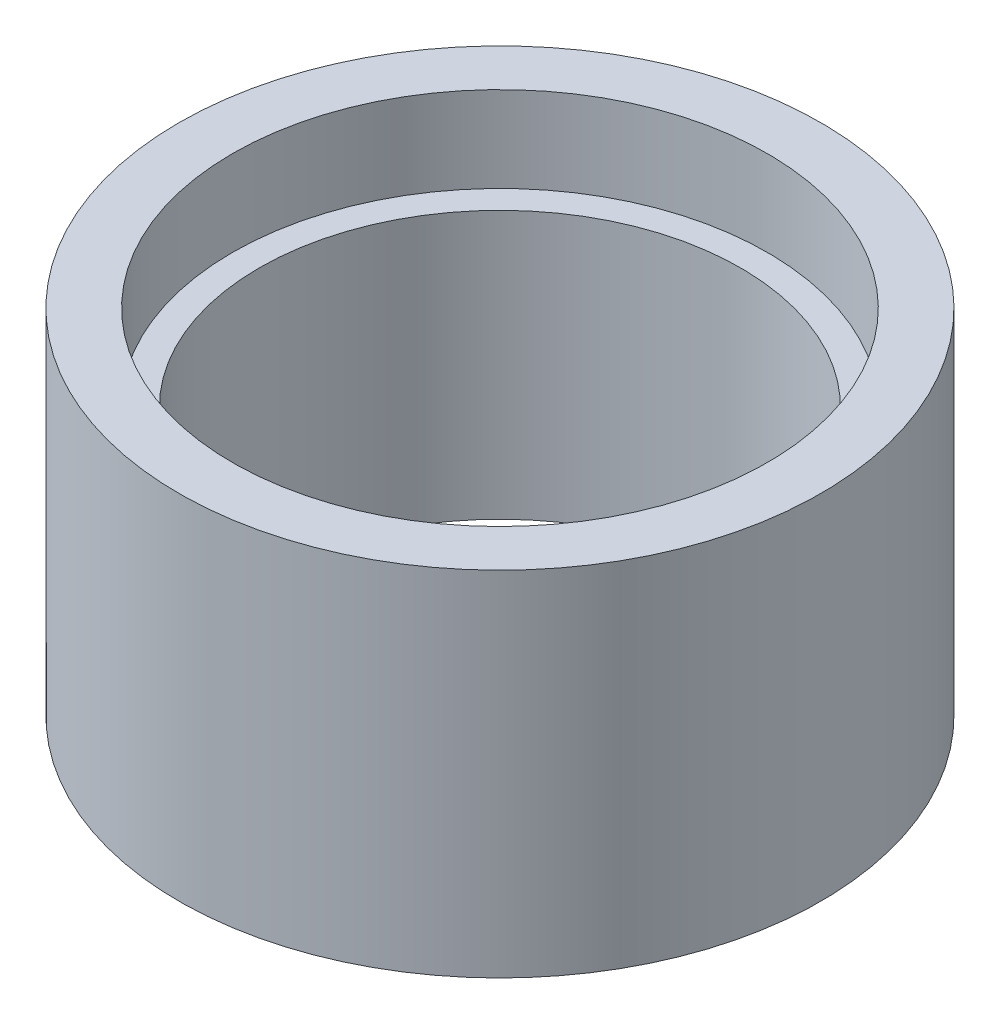
SolidWorks part; units mm, degrees
material "POM Acetal Copolymer"
ref_plane "Front" through (0, 0, 0) normal (0, 0, 1) x (1, 0, 0)
ref_plane "Top" through (0, 0, 0) normal (0, 1, 0) x (1, 0, 0)
ref_plane "Right" through (0, 0, 0) normal (1, 0, 0) x (0, 0, -1)
ref_axis "Center Axis" through (0, 0, 55) along (0, 0, -1)
sketch "Sketch1" plane through (0, 0, 0) normal (0, 0, 1) x (1, 0, 0)
  line L1 (0, 0) -> (12, 0)
  line L2 (0, 0) -> (0, -13.2)
  line L3 (0, -13.2) -> (12, -13.2)
  line L4 (12, 0) -> (12, -13.2)
  line L5 (0, 0) -> (10, 0)
  line L6 (0, 0) -> (0, -3.2)
  line L7 (0, -3.2) -> (10, -3.2)
  line L8 (10, 0) -> (10, -3.2)
  line L9 (12, -13.2) -> (9, -13.2)
  line L10 (12, -13.2) -> (12, -3.2)
  line L11 (12, -3.2) -> (9, -3.2)
  line L12 (9, -13.2) -> (9, -3.2)
  dimension "D1" = 12
  dimension "D2" = 2
  dimension "D3" = 3.2
  dimension "D4" = 1
  dimension "D5" = 10
revolve "Revolve1" add sketch "Sketch1" angle 360 about L2 region at (11, -1.6, 0) region at (10.5, -8.2, 0)
equation "\"WallThickness\" = 2mm"
equation "\"D1@Sketch1\"=\"PiezoDiameter\"/2 +\"WallThickness\""
equation "\"PiezoDiameter\"= 20mm"
equation "\"PiezoThickness\"= 2.7mm"
equation "\"BackingThickness\"= 10mm"
equation "\"MatchingThickness\"= 0.5mm"
equation "\"ShelfThickness\"= 1mm"
equation "\"D2@Sketch1\"=\"WallThickness\""
equation "\"D3@Sketch1\"=\"PiezoThickness\"+\"MatchingThickness\""
equation "\"D4@Sketch1\"=\"ShelfThickness\""
equation "\"D5@Sketch1\"=\"BackingThickness\""
